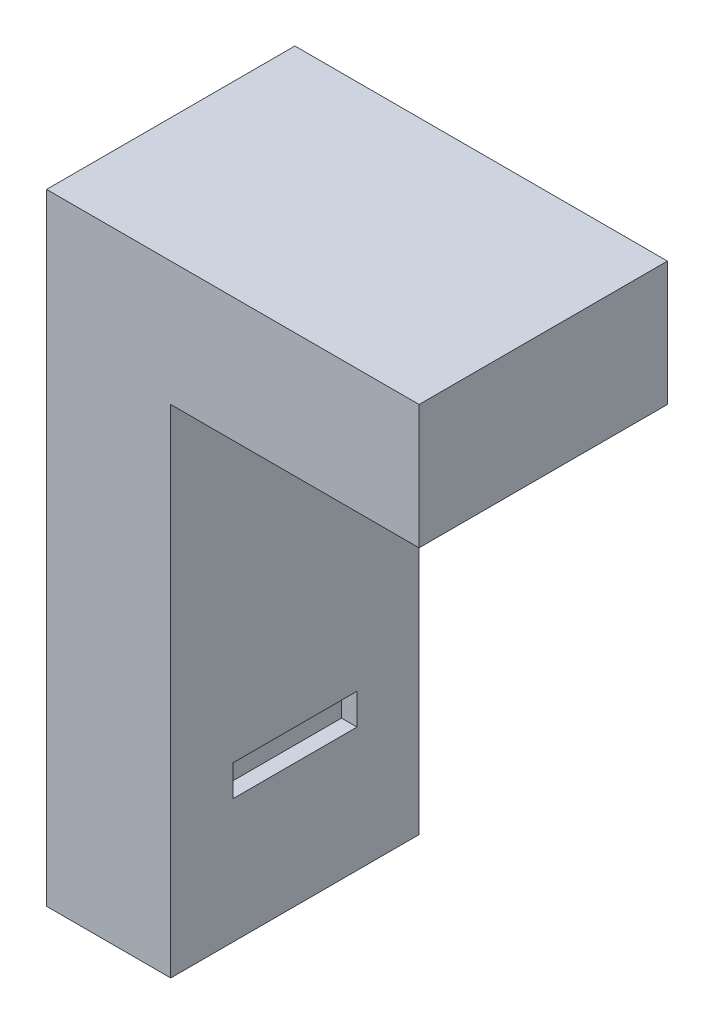
SolidWorks part; units mm, degrees
ref_plane "Front Plane" through (0, 0, 0) normal (0, 0, 1) x (1, 0, 0)
ref_plane "Top Plane" through (0, 0, 0) normal (0, 1, 0) x (1, 0, 0)
ref_plane "Right Plane" through (0, 0, 0) normal (1, 0, 0) x (0, 0, -1)
sketch "Sketch1" plane through (0, 0, 0) normal (0, 0, 1) x (1, 0, 0)
  line L0 (-12.7, 0) -> (-12.7, 63.5)
  line L1 (-12.7, 63.5) -> (25.4, 63.5)
  line L2 (25.4, 63.5) -> (25.4, 50.8)
  line L3 (25.4, 50.8) -> (0, 50.8)
  line L4 (0, 50.8) -> (0, 0)
  line L5 (0, 0) -> (-12.7, 0)
  dimension "D1" = 12.7
  dimension "D2" = 12.7
  dimension "D3" = 38.1
  dimension "D4" = 63.5
extrude "Boss-Extrude1" add sketch "Sketch1" against normal blind 25.4
sketch "Sketch2" plane through (0, 0, 0) normal (1, 0, 0) x (0, 0, -1)
  line L0 (25.4, 0) -> (0, 0) construction
  line L1 (6.35, 12.7) -> (19.05, 12.7)
  line L2 (6.35, 12.7) -> (6.35, 15.875)
  line L3 (6.35, 15.875) -> (19.05, 15.875)
  line L4 (19.05, 12.7) -> (19.05, 15.875)
  line L5 (25.4, 0) -> (25.4, 50.8) construction
  line L6 (0, 0) -> (0, 50.8) construction
  dimension "D1" = 12.7
  dimension "D2" = 6.35
  dimension "D3" = 6.35
  dimension "D4" = 3.175
extrude "Cut-Extrude1" cut sketch "Sketch2" against normal blind 1.5875
